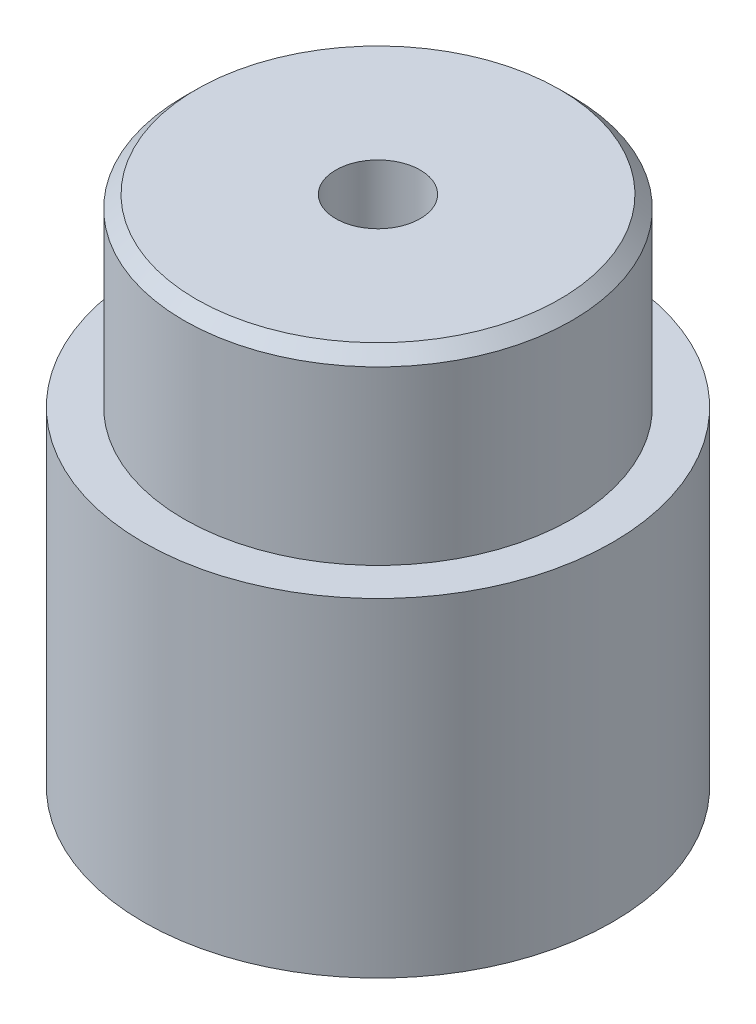
SolidWorks part; units mm, degrees
ref_plane "Front Plane" through (0, 0, 0) normal (0, 0, 1) x (1, 0, 0)
ref_plane "Top Plane" through (0, 0, 0) normal (0, 1, 0) x (1, 0, 0)
ref_plane "Right Plane" through (0, 0, 0) normal (1, 0, 0) x (0, 0, -1)
sketch "Sketch1" plane through (0, 0, 0) normal (0, 1, 0) x (1, 0, 0)
  circle A0 centre (0, 0) radius 24.257
  dimension "D1" = 48.514
extrude "Boss-Extrude1" add sketch "Sketch1" against normal blind 34
sketch "Sketch2" plane through (0, 0, 0) normal (0, 1, 0) x (1, 0, 0)
  circle A0 centre (0, 0) radius 20.066
  dimension "D1" = 40.132
extrude "Boss-Extrude2" add sketch "Sketch2" along normal blind 19.05
chamfer "Chamfer1" distance 1.27 angle 45 1 edges at (0, 19.05, 20.066)
hole_wizard "Y (0.404) Diameter Hole1" positions "Sketch3" profile "Sketch4" hole size "Y" standard "ANSI Inch"
sketch "Sketch3" plane through (0, -34, 0) normal (0, -1, 0) x (-1, 0, 0)
  point P0 (0, 0)
sketch "Sketch4" plane through (0, -34, 0) normal (1, 0, 0) x (0, 0, -1)
  line L0 (0, 0) -> (0, 14.732)
  line L1 (0, 14.732) -> (5.1308, 14.732)
  line L2 (5.1308, 14.732) -> (5.1308, 0)
  line L5 (5.1308, 0) -> (0, 0)
  line L10 (0, 14.732) -> (-5.1308, 14.732) construction
  line L11 (0, -6.35) -> (0, 107.95) construction
  dimension "Hole Dia." = 10.2616
  dimension "Hole Depth" = 14.732
  dimension "Drill Angle" = 180
hole_wizard "5/16 Clearance Hole1" positions "Sketch7" profile "Sketch8" hole size "5/16" standard "ANSI Inch" end condition through all
sketch "Sketch7" plane through (0, -19.268, 0) normal (0, -1, 0) x (-1, 0, 0)
  point P0 (0, 0)
sketch "Sketch8" plane through (0, -19.268, 0) normal (1, 0, 0) x (0, 0, -1)
  line L0 (0, 0) -> (0, 38.318)
  line L1 (0, 38.318) -> (4.365, 38.318)
  line L2 (4.365, 38.318) -> (4.365, 0)
  line L5 (4.365, 0) -> (0, 0)
  line L11 (0, -6.35) -> (0, 107.95) construction
  dimension "Thru Hole Dia." = 8.73
  dimension "Thru Hole Depth" = 38.318
